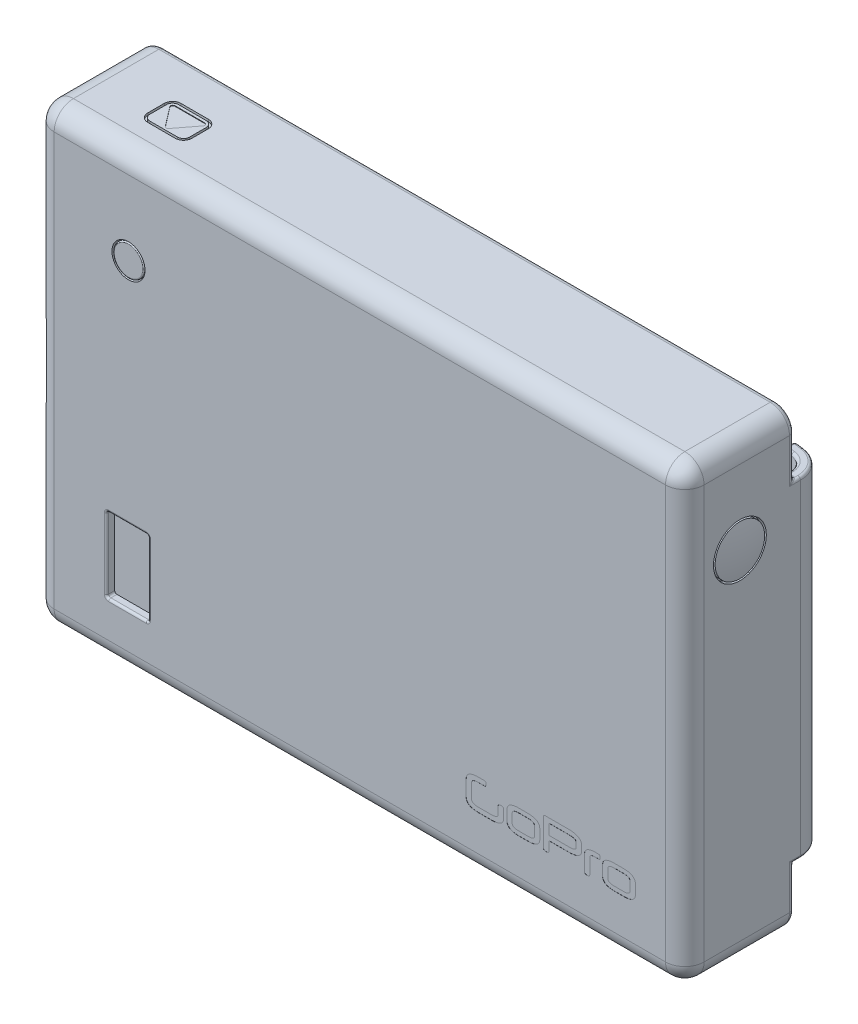
SolidWorks part; units mm, degrees
note: The reader was unsure of these and kept them because the rebuilt part matched: shared geometry of "Sketch5<3>", "Sketch6<3>", "Sketch7<3>", "Sketch11<3>", "Sketch12<3>", "Sketch13<3>", "Sketch13<4>".
ref_plane "Front Plane" through (0, 0, 0) normal (0, 0, 1) x (1, 0, 0)
ref_plane "Top Plane" through (0, 0, 0) normal (0, 1, 0) x (1, 0, 0)
ref_plane "Right Plane" through (0, 0, 0) normal (1, 0, 0) x (0, 0, -1)
sketch "Sketch1" plane through (0, 0, 0) normal (0, 0, 1) x (1, 0, 0)
  line L1 (0, 0) -> (59, 0)
  line L2 (0, 0) -> (0, 41)
  line L3 (0, 41) -> (59, 41)
  line L4 (59, 0) -> (59, 41)
  dimension "D1" = 59
  dimension "D2" = 41
extrude "Boss-Extrude1" add sketch "Sketch1" along normal blind 10
fillet "Fillet1" radius 1.75 8 edges at (59, 0, 5) (59, 41, 5) (0, 0, 5) (0, 41, 5) (29.5, 41, 10) (59, 20.5, 10) (29.5, 0, 10) (0, 20.5, 10)
sketch "Sketch2" plane through (0, 0, 10) normal (0, 0, 1) x (1, 0, 0)
  line L0 (0, 1.75) -> (0, 39.25) construction
  line L1 (6.5, 5) -> (10.3, 5)
  line L2 (6.5, 5) -> (6.5, 11.8)
  line L3 (6.5, 11.8) -> (10.3, 11.8)
  line L4 (10.3, 5) -> (10.3, 11.8)
  line L5 (57.25, 0) -> (1.75, 0) construction
  dimension "D1" = 6.8
  dimension "D2" = 6.5
  dimension "D3" = 3.8
  dimension "D4" = 5
extrude "Cut-Extrude1" cut sketch "Sketch2" against normal blind 0.75
fillet "Fillet2" radius 0.2 8 edges at (10.3, 11.8, 9.625) (6.5, 11.8, 9.625) (6.5, 5, 9.625) (10.3, 5, 9.625) (8.4, 5, 10) (10.3, 8.4, 10) (8.4, 11.8, 10) (6.5, 8.4, 10)
sketch "Sketch3" plane through (0, 0, 10) normal (0, 0, 1) x (1, 0, 0)
  line L0 (1.75, 41) -> (57.25, 41) construction
  line L1 (0, 1.75) -> (0, 39.25) construction
  circle A0 centre (8.5, 32.5) radius 1.5
  circle A1 centre (8.5, 32.5) radius 1.4
  dimension "D1" = 3
  dimension "D2" = 2.8
  dimension "D3" = 8.5
  dimension "D4" = 8.5
extrude "Cut-Extrude2" cut sketch "Sketch3" against normal blind 0.75
fillet "Fillet3" radius 0.1 1 edges at (9.9, 32.5, 10)
sketch "Sketch4" plane through (0, 0, 10) normal (0, 0, 1) x (1, 0, 0)
  line L0 (57.25, 0) -> (1.75, 0) construction
  line L1 (59, 39.25) -> (59, 1.75) construction
  text T0 "GoPro\r\n" font "Neuropol" height in points 10
  dimension "D1" = 5
  dimension "D2" = 20
extrude "Cut-Extrude3" cut sketch "Sketch4" against normal blind 0.01
sketch "Sketch5" plane through (0, 41, 0) normal (0, 1, 0) x (1, 0, 0)
  line L0 (7, -6.55) -> (9.5, -6.55)
  line L1 (7, -6.75) -> (9.5, -6.75)
  line L2 (6.25, -6) -> (6.25, -4.5)
  line L3 (7, -3.75) -> (9.5, -3.75)
  line L4 (10.25, -6) -> (10.25, -4.5)
  line L5 (10.05, -6) -> (10.05, -4.5)
  line L6 (7, -3.95) -> (9.5, -3.95)
  line L7 (6.45, -6) -> (6.45, -4.5)
  line L8 (0, -8.25) -> (0, 0) construction
  line L9 (57.25, -10) -> (1.75, -10) construction
  line L10 (6.7719, -4.5218) -> (8.1163, -6.2739)
  line L11 (8.4337, -6.2739) -> (9.7781, -4.5218)
  line L12 (9.6194, -4.2) -> (6.9306, -4.2)
  arc A0 (6.25, -4.5) -> (7, -3.75) centre (7, -4.5) cw
  arc A1 (9.5, -3.75) -> (10.25, -4.5) centre (9.5, -4.5) cw
  arc A2 (9.5, -6.75) -> (10.25, -6) centre (9.5, -6) ccw
  arc A3 (7, -6.75) -> (6.25, -6) centre (7, -6) cw
  arc A4 (9.5, -6.55) -> (10.05, -6) centre (9.5, -6) ccw
  arc A5 (9.5, -3.95) -> (10.05, -4.5) centre (9.5, -4.5) cw
  arc A6 (6.45, -4.5) -> (7, -3.95) centre (7, -4.5) cw
  arc A7 (7, -6.55) -> (6.45, -6) centre (7, -6) cw
  arc A8 (8.1163, -6.2739) -> (8.4337, -6.2739) centre (8.275, -6.1521) ccw
  arc A9 (9.7781, -4.5218) -> (9.6194, -4.2) centre (9.6194, -4.4) ccw
  arc A10 (6.7719, -4.5218) -> (6.9306, -4.2) centre (6.9306, -4.4) cw
  point P35 (10.025, -4.2)
  point P38 (6.525, -4.2)
  dimension "D1" = 0.75
  dimension "D11" = 0.2
  dimension "D3" = 4
  dimension "D4" = 3
  dimension "D5" = 6.25
  dimension "D6" = 3.25
  dimension "D7" = 75
  dimension "D8" = 3.5
  dimension "D9" = 0.075
  dimension "D10" = 0.25
  dimension "D2" = 0.2
extrude "Cut-Extrude4" cut sketch "Sketch5" against normal blind 0.2 contours A3 L1 A2 L4 A1 L3 A0 L2 L0 A7 L7 A6 L6 A5 L5 A4
extrude "Cut-Extrude5" cut sketch "Sketch5<3>" against normal blind 0.05 contours A10 L10 A8 L11 A9 L12
sketch "Sketch5<3>" plane through (0, 41, 0) normal (0, 1, 0) x (1, 0, 0) same geometry as "Sketch5"
sketch "Sketch6" plane through (0, 0, 0) normal (-1, 0, 0) x (0, 0, 1)
  line L0 (3.45, 10.3) -> (3.45, 7.7)
  line L1 (3.25, 10.3) -> (3.25, 7.7)
  line L2 (3.95, 11) -> (5.55, 11)
  line L3 (6.25, 10.3) -> (6.25, 7.7)
  line L4 (3.95, 7) -> (5.55, 7)
  line L5 (3.95, 7.2) -> (5.55, 7.2)
  line L6 (6.05, 10.3) -> (6.05, 7.7)
  line L7 (3.95, 10.8) -> (5.55, 10.8)
  line L8 (4.0218, 7.5219) -> (5.7739, 8.8663)
  line L9 (5.7739, 9.1837) -> (4.0218, 10.5281)
  line L10 (3.7, 10.3694) -> (3.7, 7.6806)
  line L11 (0, 39.25) -> (0, 1.75) construction
  line L12 (8.25, 0) -> (0, 0) construction
  arc A0 (5.55, 11) -> (6.25, 10.3) centre (5.55, 10.3) cw
  arc A1 (6.25, 7.7) -> (5.55, 7) centre (5.55, 7.7) cw
  arc A2 (3.25, 7.7) -> (3.95, 7) centre (3.95, 7.7) ccw
  arc A3 (3.25, 10.3) -> (3.95, 11) centre (3.95, 10.3) cw
  arc A4 (3.45, 7.7) -> (3.95, 7.2) centre (3.95, 7.7) ccw
  arc A5 (6.05, 7.7) -> (5.55, 7.2) centre (5.55, 7.7) cw
  arc A6 (5.55, 10.8) -> (6.05, 10.3) centre (5.55, 10.3) cw
  arc A7 (3.45, 10.3) -> (3.95, 10.8) centre (3.95, 10.3) cw
  arc A8 (5.7739, 8.8663) -> (5.7739, 9.1837) centre (5.6521, 9.025) ccw
  arc A9 (4.0218, 10.5281) -> (3.7, 10.3694) centre (3.9, 10.3694) ccw
  arc A10 (4.0218, 7.5219) -> (3.7, 7.6806) centre (3.9, 7.6806) cw
  point P28 (3.7, 10.775)
  point P31 (3.7, 7.275)
  dimension "D1" = 0.5
  dimension "D2" = 0.7
  dimension "D4" = 0.2
  dimension "D3" = 3.5
  dimension "D5" = 3
  dimension "D6" = 4
  dimension "D7" = 0.25
  dimension "D8" = 0.075
  dimension "D9" = 75
  dimension "D10" = 3.25
  dimension "D11" = 7
extrude "Cut-Extrude6" cut sketch "Sketch6" against normal blind 0.05 contours A10 L8 A8 L9 A9 L10
extrude "Cut-Extrude7" cut sketch "Sketch6<3>" against normal blind 0.2 contours A3 L1 A2 L4 A1 L3 A0 L2 L0 A7 L7 A6 L6 A5 L5 A4
sketch "Sketch6<3>" plane through (0, 0, 0) normal (-1, 0, 0) x (0, 0, 1) same geometry as "Sketch6"
sketch "Sketch7" plane through (0, 0, 0) normal (0, -1, 0) x (1, 0, 0)
  line L0 (6.25, 3.7) -> (8.75, 3.7)
  line L1 (6.25, 3.5) -> (8.75, 3.5)
  line L2 (5.5, 4.25) -> (5.5, 5.75)
  line L3 (6.25, 6.5) -> (8.75, 6.5)
  line L4 (9.5, 4.25) -> (9.5, 5.75)
  line L5 (9.3, 4.25) -> (9.3, 5.75)
  line L6 (6.25, 6.3) -> (8.75, 6.3)
  line L7 (5.7, 4.25) -> (5.7, 5.75)
  line L8 (5.9719, 4.2218) -> (7.3163, 5.9739)
  line L9 (7.6337, 5.9739) -> (8.9781, 4.2218)
  line L10 (8.8194, 3.9) -> (6.1306, 3.9)
  line L11 (0, 0) -> (0, 8.25) construction
  line L12 (1.75, 0) -> (57.25, 0) construction
  arc A0 (5.5, 5.75) -> (6.25, 6.5) centre (6.25, 5.75) cw
  arc A1 (8.75, 6.5) -> (9.5, 5.75) centre (8.75, 5.75) cw
  arc A2 (8.75, 3.5) -> (9.5, 4.25) centre (8.75, 4.25) ccw
  arc A3 (6.25, 3.5) -> (5.5, 4.25) centre (6.25, 4.25) cw
  arc A4 (8.75, 3.7) -> (9.3, 4.25) centre (8.75, 4.25) ccw
  arc A5 (8.75, 6.3) -> (9.3, 5.75) centre (8.75, 5.75) cw
  arc A6 (5.7, 5.75) -> (6.25, 6.3) centre (6.25, 5.75) cw
  arc A7 (6.25, 3.7) -> (5.7, 4.25) centre (6.25, 4.25) cw
  arc A8 (8.9781, 4.2218) -> (8.8194, 3.9) centre (8.8194, 4.1) cw
  arc A9 (7.3163, 5.9739) -> (7.6337, 5.9739) centre (7.475, 5.8521) cw
  arc A10 (5.9719, 4.2218) -> (6.1306, 3.9) centre (6.1306, 4.1) ccw
  point P28 (9.225, 3.9)
  point P33 (5.725, 3.9)
  dimension "D1" = 0.75
  dimension "D6" = 3.5
  dimension "D9" = 0.2
  dimension "D2" = 4
  dimension "D3" = 3
  dimension "D4" = 0.2
  dimension "D5" = 75
  dimension "D7" = 0.075
  dimension "D8" = 0.2
  dimension "D10" = 5.5
  dimension "D11" = 3.5
extrude "Cut-Extrude8" cut sketch "Sketch7" against normal blind 0.05 contours L8 A10 L10 A8 L9 A9
extrude "Cut-Extrude9" cut sketch "Sketch7<3>" against normal blind 0.2 contours A3 L1 A2 L4 A1 L3 A0 L2 L0 A7 L7 A6 L6 A5 L5 A4
sketch "Sketch7<3>" plane through (0, 0, 0) normal (0, -1, 0) x (1, 0, 0) same geometry as "Sketch7"
sketch "Sketch8" plane through (59, 0, 0) normal (1, 0, 0) x (0, 0, -1)
  line L1 (-8.25, 41) -> (0, 41) construction
  line L2 (-10, 1.75) -> (-10, 39.25) construction
  circle A0 centre (-5, 32.5) radius 2.25
  circle A1 centre (-5, 32.5) radius 2.4
  dimension "D1" = 4.8
  dimension "D2" = 4.5
  dimension "D3" = 5
  dimension "D4" = 8.5
extrude "Cut-Extrude10" cut sketch "Sketch8" against normal blind 0.5
ref_plane "Plane1" through (0, 32.5, 0) normal (0, 1, 0) x (1, 0, 0)
sketch "Sketch9" plane through (0, 32.5, 0) normal (0, 1, 0) x (1, 0, 0)
  line L0 (59, -5) -> (59, -2.75)
  line L1 (59, -7.25) -> (59, -2.75) construction
  line L2 (59, -5) -> (59.2, -5)
  line L3 (59.2, -5) -> (59.2, -2.75) construction
  arc A0 (59, -2.75) -> (59.2, -5) centre (46.4438, -5) cw
  dimension "D1" = 0.2
revolve "Revolve1" add sketch "Sketch9" angle 360 about L2
sketch "Sketch11" plane through (0, 0, 0) normal (-1, 0, 0) x (0, 0, 1)
  line L0 (0, 20.5) -> (8.25, 20.5) construction
  line L1 (0, 39.25) -> (0, 1.75) construction
  line L2 (8.25, 1.75) -> (8.25, 39.25) construction
  line L3 (5.5, 17.875) -> (5.5, 23.125)
  line L4 (5.75, 23.375) -> (6.4567, 23.375)
  line L5 (6.5407, 23.3895) -> (7.2093, 23.6281)
  line L6 (7.2933, 23.6426) -> (8.25, 23.6426)
  line L7 (8.5, 23.3926) -> (8.5, 17.6074)
  line L8 (10, 39.25) -> (10, 1.75) construction
  line L9 (7.2933, 17.3574) -> (8.25, 17.3574)
  line L10 (6.5407, 17.6105) -> (7.2093, 17.3719)
  line L11 (5.75, 17.625) -> (6.4567, 17.625)
  line L12 (5.1, 17.875) -> (5.1, 23.125)
  line L13 (5.75, 23.775) -> (6.4308, 23.775)
  line L14 (6.4308, 23.775) -> (7.0748, 24.0048)
  line L15 (7.2933, 24.0426) -> (8.25, 24.0426)
  line L16 (8.9, 23.3926) -> (8.9, 17.6074)
  line L17 (7.2933, 16.9574) -> (8.25, 16.9574)
  line L18 (6.4308, 17.225) -> (7.0748, 16.9952)
  line L19 (5.75, 17.225) -> (6.4308, 17.225)
  line L20 (4.7, 17.875) -> (4.7, 23.125)
  line L21 (5.75, 24.175) -> (6.3616, 24.175)
  line L22 (6.3616, 24.175) -> (6.9404, 24.3815)
  line L23 (7.2933, 24.4426) -> (8.25, 24.4426)
  line L24 (9.3, 23.3926) -> (9.3, 17.6074)
  line L25 (7.2933, 16.5574) -> (8.25, 16.5574)
  line L26 (6.3616, 16.825) -> (6.9404, 16.6185)
  line L27 (5.75, 16.825) -> (6.3616, 16.825)
  arc A0 (8.25, 23.6426) -> (8.5, 23.3926) centre (8.25, 23.3926) cw
  arc A1 (7.2093, 23.6281) -> (7.2933, 23.6426) centre (7.2933, 23.3926) cw
  arc A2 (6.4567, 23.375) -> (6.5407, 23.3895) centre (6.4567, 23.625) ccw
  arc A3 (5.5, 23.125) -> (5.75, 23.375) centre (5.75, 23.125) cw
  arc A4 (5.5, 17.875) -> (5.75, 17.625) centre (5.75, 17.875) ccw
  arc A5 (6.4567, 17.625) -> (6.5407, 17.6105) centre (6.4567, 17.375) cw
  arc A6 (7.2093, 17.3719) -> (7.2933, 17.3574) centre (7.2933, 17.6074) ccw
  arc A7 (8.25, 17.3574) -> (8.5, 17.6074) centre (8.25, 17.6074) ccw
  arc A8 (5.1, 23.125) -> (5.75, 23.775) centre (5.75, 23.125) cw
  arc A9 (6.4308, 23.775) -> (6.4308, 23.775) centre (6.4308, 23.775) ccw
  arc A10 (7.0748, 24.0048) -> (7.2933, 24.0426) centre (7.2933, 23.3926) cw
  arc A11 (8.25, 24.0426) -> (8.9, 23.3926) centre (8.25, 23.3926) cw
  arc A12 (8.25, 16.9574) -> (8.9, 17.6074) centre (8.25, 17.6074) ccw
  arc A13 (7.0748, 16.9952) -> (7.2933, 16.9574) centre (7.2933, 17.6074) ccw
  arc A14 (6.4308, 17.225) -> (6.4308, 17.225) centre (6.4308, 17.225) cw
  arc A15 (5.1, 17.875) -> (5.75, 17.225) centre (5.75, 17.875) ccw
  arc A16 (4.7, 23.125) -> (5.75, 24.175) centre (5.75, 23.125) cw
  arc A17 (6.3616, 24.175) -> (6.3616, 24.175) centre (6.3616, 24.175) ccw
  arc A18 (6.9404, 24.3815) -> (7.2933, 24.4426) centre (7.2933, 23.3926) cw
  arc A19 (8.25, 24.4426) -> (9.3, 23.3926) centre (8.25, 23.3926) cw
  arc A20 (8.25, 16.5574) -> (9.3, 17.6074) centre (8.25, 17.6074) ccw
  arc A21 (6.9404, 16.6185) -> (7.2933, 16.5574) centre (7.2933, 17.6074) ccw
  arc A22 (6.3616, 16.825) -> (6.3616, 16.825) centre (6.3616, 16.825) cw
  arc A23 (4.7, 17.875) -> (5.75, 16.825) centre (5.75, 17.875) ccw
  point P14 (8.5, 23.6426)
  point P17 (7.25, 23.6426)
  point P20 (6.5, 23.375)
  point P23 (5.5, 23.375)
  point P27 (5.5, 20.5)
  point P28 (8.5, 20.5)
  point P38 (5.5, 17.625)
  point P39 (6.5, 17.625)
  point P40 (7.25, 17.3574)
  point P41 (8.5, 17.3574)
  line M17 (8.25, 1.75) -> (8.25, 39.25)
  dimension "D6" = 0.25
  dimension "D1" = 2.875
  dimension "D2" = 1
  dimension "D3" = 3
  dimension "D4" = 1.25
  dimension "D5" = 3.1426
  dimension "D7" = 1.5
  dimension "D8" = 0.4
  dimension "D9" = 0.4
extrude "Cut-Extrude11" cut sketch "Sketch11" against normal blind 3 contours L0 L20 A23 L27 L26 A21 L25 A20 A12 L17 A13 L18 L19 A15 L12 M17 | L20 L0 L12 A8 L13 L14 A10 L15 A11 A19 L23 A18 L22 L21 A16 M17 | A20 L24 A19 A11 L16 A12 M17 | L0 L3 A4 L11 A5 L10 A6 L9 A7 L7 | L3 L0 L7 A0 L6 A1 L5 A2 L4 A3 | A7 L7 A0 M17
extrude "Cut-Extrude12" cut sketch "Sketch11<3>" against normal blind 0.15 contours L0 L12 A15 L19 L18 A13 L17 A12 L7 A7 L9 A6 L10 A5 L11 A4 L3 M17 | L12 L0 L3 A3 L4 A2 L5 A1 L6 A0 L7 A11 L15 A10 L14 L13 A8 M17 | A12 L16 A11 M17
sketch "Sketch11<3>" plane through (0, 0, 0) normal (-1, 0, 0) x (0, 0, 1) same geometry as "Sketch11"
fillet "Fillet4" radius 0.2 23 edges at (3, 16.7217, 6.651) (3, 16.5728, 7.1142) (3, 16.5574, 7.7716) (3, 16.8649, 8.9925) (3, 20.5, 9.3) (3, 24.1351, 8.9925) (3, 24.4426, 7.7716) (3, 24.4272, 7.1142) (0, 16.5728, 7.1142) (3, 24.2783, 6.651) (0, 24.4426, 7.7716) (0, 24.4272, 7.1142) (0, 24.2783, 6.651) (0, 24.175, 6.0558) (0, 23.8675, 5.0075) (0.1046, 24.2571, 8.8459) (0.35, 20.5, 9.3) (0.1046, 16.7429, 8.8459) (0, 16.5574, 7.7716) (0, 16.7217, 6.651) (0, 16.825, 6.0558) (0, 17.1325, 5.0075) (0, 20.5, 4.7)
sketch "Sketch12" plane through (3, 0, 0) normal (-1, 0, 0) x (0, 0, 1)
  line L0 (5.5, 20.5) -> (8.5, 20.5) construction
  line L1 (5.5, 17.875) -> (5.5, 23.125) construction
  line L2 (8.5, 23.3926) -> (8.5, 17.6074) construction
  line L3 (5.9, 18.8) -> (5.9, 22.2)
  line L4 (5.9, 22.2) -> (6.5, 22.8)
  line L5 (6.5, 22.8) -> (7.5, 22.8)
  line L6 (7.5, 22.8) -> (7.5, 18.2)
  line L7 (6.4, 20.325) -> (6.4, 20.675)
  line L8 (6.4, 20.675) -> (7, 20.675)
  line L9 (7, 20.675) -> (7, 20.325)
  line L10 (6.4, 21.125) -> (7, 21.125)
  line L11 (7, 21.125) -> (7, 21.475)
  line L12 (7, 21.475) -> (6.4, 21.475)
  line L13 (6.4, 21.475) -> (6.4, 21.125)
  line L14 (6.4, 22.275) -> (6.4, 21.925)
  line L15 (6.4, 21.925) -> (7, 21.925)
  line L16 (7, 21.925) -> (7, 22.275)
  line L17 (7, 22.275) -> (6.4, 22.275)
  line L18 (6.55, 20.325) -> (6.55, 20.675)
  line L19 (6.9, 20.325) -> (6.9, 20.675)
  line L20 (6.9, 21.125) -> (6.9, 21.475)
  line L21 (6.55, 21.125) -> (6.55, 21.475)
  line L26 (6.55, 21.925) -> (6.55, 22.275)
  line L27 (6.9, 21.925) -> (6.9, 22.275)
  line L28 (6.9, 19.075) -> (6.9, 18.725)
  line L29 (6.55, 19.075) -> (6.55, 18.725)
  line L30 (6.55, 19.875) -> (6.55, 19.525)
  line L31 (6.9, 19.875) -> (6.9, 19.525)
  line L32 (7, 18.725) -> (6.4, 18.725)
  line L33 (7, 19.075) -> (7, 18.725)
  line L34 (6.4, 19.075) -> (7, 19.075)
  line L35 (6.4, 18.725) -> (6.4, 19.075)
  line L36 (6.4, 19.525) -> (6.4, 19.875)
  line L37 (7, 19.525) -> (6.4, 19.525)
  line L38 (7, 19.875) -> (7, 19.525)
  line L39 (6.4, 19.875) -> (7, 19.875)
  line L40 (6.4, 20.325) -> (7, 20.325)
  line L41 (6.5, 18.2) -> (7.5, 18.2)
  line L42 (5.9, 18.8) -> (6.5, 18.2)
  point P6 (6.4, 18.9)
  point P20 (6.4, 20.5)
  point P25 (6.4, 21.3)
  point P33 (6.4, 22.1)
  point P55 (6.9, 20.5)
  point P56 (6.55, 20.5)
  point P65 (7, 20.5)
  point P66 (6.4, 20.5)
  point P67 (7.5, 20.5)
  point P69 (5.9, 20.5)
  point P70 (6.4, 19.7)
  dimension "D2" = 0.35
  dimension "D3" = 2.3
  dimension "D4" = 1.6
  dimension "D5" = 0.8
  dimension "D6" = 45
  dimension "D7" = 0.6
  dimension "D8" = 0.5
  dimension "D9" = 1
  dimension "D10" = 0.35
  dimension "D11" = 0.1
  dimension "D12" = 0.175
  dimension "D13" = 1
  dimension "D14" = 0.8
  dimension "D1" = 2
extrude "Boss-Extrude2" add sketch "Sketch12" along normal blind 2.5 contours L0 L3 L42 L41 L6 L9 L40 L7 L36 L39 L38 L37 L32 L35 L34 L33 | L3 L0 L7 L8 L9 L6 L5 L4 L17 L16 L15 L14 L13 L12 L11 L10
extrude "Boss-Extrude3" add sketch "Sketch12<3>" along normal blind 2.7 contours L34 L29 L32 L28 | L39 L30 L37 L31 | L0 L18 L40 L19 | L18 L0 L19 L8 | L21 L10 L20 L12 | L15 L27 L17 L26
sketch "Sketch12<3>" plane through (3, 0, 0) normal (-1, 0, 0) x (0, 0, 1) same geometry as "Sketch12"
chamfer "Chamfer1" distance 0.1 angle 45 20 edges at (0.3, 22.1, 6.55) (0.3, 22.275, 6.725) (0.3, 22.1, 6.9) (0.3, 21.925, 6.725) (0.3, 21.475, 6.725) (0.3, 21.3, 6.9) (0.3, 21.125, 6.725) (0.3, 21.3, 6.55) (0.3, 20.325, 6.725) (0.3, 20.5, 6.55) (0.3, 20.675, 6.725) (0.3, 20.5, 6.9) (0.3, 19.7, 6.9) (0.3, 19.525, 6.725) (0.3, 19.7, 6.55) (0.3, 19.875, 6.725) (0.3, 18.9, 6.9) (0.3, 18.725, 6.725) (0.3, 18.9, 6.55) (0.3, 19.075, 6.725)
sketch "Sketch13" plane through (0, 0, 0) normal (0, 0, -1) x (-1, 0, 0)
  line L0 (-5.35, 30.95) -> (-3.35, 30.95)
  line L1 (-3.35, 30.95) -> (-3.35, 30.2)
  line L2 (-3.35, 30.2) -> (-2.55, 30.2)
  line L3 (-2.55, 30.2) -> (-2.55, 10.8)
  line L4 (-2.55, 10.8) -> (-3.35, 10.8)
  line L5 (-3.35, 10.8) -> (-3.35, 10.05)
  line L6 (-3.35, 10.05) -> (-5.35, 10.05)
  line L7 (-5.35, 10.05) -> (-5.35, 30.95)
  line L8 (-5.15, 10.25) -> (-5.15, 30.75)
  line L9 (-5.15, 30.75) -> (-3.55, 30.75)
  line L10 (-3.55, 30.75) -> (-3.55, 30)
  line L11 (-3.55, 30) -> (-2.75, 30)
  line L12 (-2.75, 30) -> (-2.75, 11)
  line L13 (-2.75, 11) -> (-3.55, 11)
  line L14 (-3.55, 11) -> (-3.55, 10.25)
  line L15 (-3.55, 10.25) -> (-5.15, 10.25)
  line L16 (-3.55, 30) -> (-3.55, 29.55)
  line L17 (-3.55, 29.55) -> (-5.15, 29.55)
  line L18 (-3.55, 11) -> (-3.55, 11.45)
  line L19 (-3.55, 11.45) -> (-5.15, 11.45)
  line L20 (-59, 20.5) -> (0, 20.5) construction
  line L21 (-59, 1.75) -> (-59, 39.25) construction
  line L22 (0, 39.25) -> (0, 1.75) construction
  point P26 (-5.35, 20.5)
  dimension "D2" = 1.6
  dimension "D3" = 2.4
  dimension "D4" = 0.75
  dimension "D5" = 1.2
  dimension "D6" = 19
  dimension "D7" = 2.75
  dimension "D1" = 0.2
extrude "Boss-Extrude4" [suppressed] add sketch "Sketch13" along normal blind 4.8 contours L8 L20 L12 L11 L16 L17 | L20 L8 L19 L18 L13 L12
extrude "Boss-Extrude5" add sketch "Sketch13<3>" along normal blind 6 contours L17 L16 L10 L9 L8 | L18 L19 L8 L15 L14
sketch "Sketch13<3>" plane through (0, 0, 0) normal (0, 0, -1) x (-1, 0, 0) same geometry as "Sketch13"
chamfer "Chamfer2" distance 0.8 angle 45 6 edges at (3.55, 30.15, -6) (5.15, 30.15, -6) (4.35, 30.75, -6) (3.55, 10.85, -6) (5.15, 10.85, -6) (4.35, 10.25, -6)
extrude "Cut-Extrude13" cut sketch "Sketch13<4>" against normal blind 0.2 contours L20 L7 L6 L5 L4 L3 L12 L13 L14 L15 L8 | L7 L20 L8 L9 L10 L11 L12 L3 L2 L1 L0
sketch "Sketch13<4>" plane through (0, 0, 0) normal (0, 0, -1) x (-1, 0, 0) same geometry as "Sketch13"
sketch "Sketch14" [suppressed] plane through (5.15, 0, 0) normal (1, 0, 0) x (0, 0, -1)
  line L0 (4.8, 29.55) -> (-0.2, 29.55)
  line L1 (-0.2, 10.25) -> (-0.2, 30.75) construction
  line L2 (4.8, 11.45) -> (-0.2, 11.45)
split line "Split Line3" [suppressed]
sketch "Sketch15" plane through (0, 0, 0) normal (0, 0, -1) x (-1, 0, 0)
  line L0 (-1.75, 0) -> (-57.25, 0) construction
  line L1 (0, 39.25) -> (0, 1.75) construction
  circle A0 centre (-4, 36.5) radius 1.5
  circle A1 centre (-4, 4) radius 1.5
  dimension "D1" = 3
  dimension "D2" = 32.5
  dimension "D3" = 4
  dimension "D4" = 4
extrude "Cut-Extrude14" cut sketch "Sketch15" against normal blind 1.4
ref_plane "Plane2" through (0, 20.5, 0) normal (0, -1, 0) x (-1, 0, 0)
sketch "Sketch16" plane through (0, 20.5, 0) normal (0, -1, 0) x (-1, 0, 0)
  line L0 (-59, 0) -> (-59, 0.5)
  line L1 (-58, 0) -> (-58, 0.5)
  line L2 (-56.8373, 2.9771) -> (-55.9349, 3.1)
  line L3 (-55.9349, 3.1) -> (-55.8, 2.1091)
  line L4 (-56.7024, 1.9863) -> (-55.8, 2.1091)
  line L5 (-59, 0) -> (-58, 0)
  arc A0 (-59, 0.5) -> (-56.8373, 2.9771) centre (-56.5, 0.5) cw
  arc A1 (-58, 0.5) -> (-56.7024, 1.9863) centre (-56.5, 0.5) cw
  arc A2 (-58, 0.5) -> (-56.7024, 1.9863) centre (-56.5, 0.5) cw construction
  dimension "D2" = 2.5
  dimension "D4" = 3.1
  dimension "D5" = 3.2
  dimension "D1" = 0.5
  dimension "D6" = 1
  dimension "D3" = 1
extrude "Boss-Extrude6" add sketch "Sketch16" along normal blind 15 and the other way blind 15
fillet "Fillet6" radius 0.25 16 edges at (58, 35.5, -0.25) (56.2512, 35.5, -2.0477) (58, 5.5, -0.25) (56.2512, 5.5, -2.0477) (56.3861, 35.5, -3.0386) (56.3861, 5.5, -3.0386) (57.6299, 35.5, -1.4865) (57.6299, 5.5, -1.4865) (55.8675, 35.5, -2.6046) (55.8, 20.5, -2.1091) (55.8675, 5.5, -2.6046) (55.9349, 20.5, -3.1) (58.3832, 35.5, -2.1442) (58.3832, 5.5, -2.1442)
fillet "Fillet7" radius 0.5 9 edges at (58.4874, 40.4874, 0) (29.5, 41, 0) (0.5126, 40.4874, 0) (0, 20.5, 0) (0.5126, 0.5126, 0) (29.5, 0, 0) (58.4874, 0.5126, 0)
fillet "Fillet8" radius 0.25 11 edges at (58.935, 35.4182, 0.2535) (58.6294, 35.5, 0.017) (58.0732, 35.4268, 0) (58.935, 5.5818, 0.2535) (58.6294, 5.5, 0.017) (58.0732, 5.5732, 0) (2.5, 4, 0) (2.5, 36.5, 0) (58, 20.5, 0)
